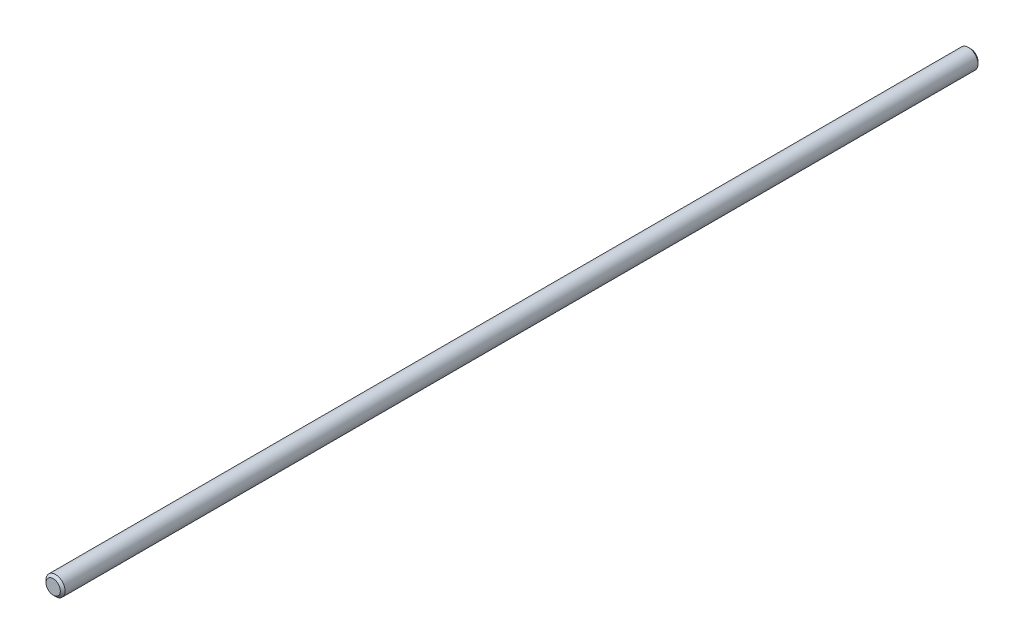
SolidWorks part; units mm, degrees
ref_plane "Front Plane" through (0, 0, 0) normal (0, 0, 1) x (1, 0, 0)
ref_plane "Top Plane" through (0, 0, 0) normal (0, 1, 0) x (1, 0, 0)
ref_plane "Right Plane" through (0, 0, 0) normal (1, 0, 0) x (0, 0, -1)
sketch "Sketch1" plane through (0, 0, 0) normal (0, 0, 1) x (1, 0, 0)
  circle A0 centre (0, 0) radius 4
  dimension "D1" = 8
extrude "Boss-Extrude1" add sketch "Sketch1" along normal blind 384
chamfer "Chamfer1" distance 1 angle 45 2 edges at (4, 0, 384) (4, 0, 0)
